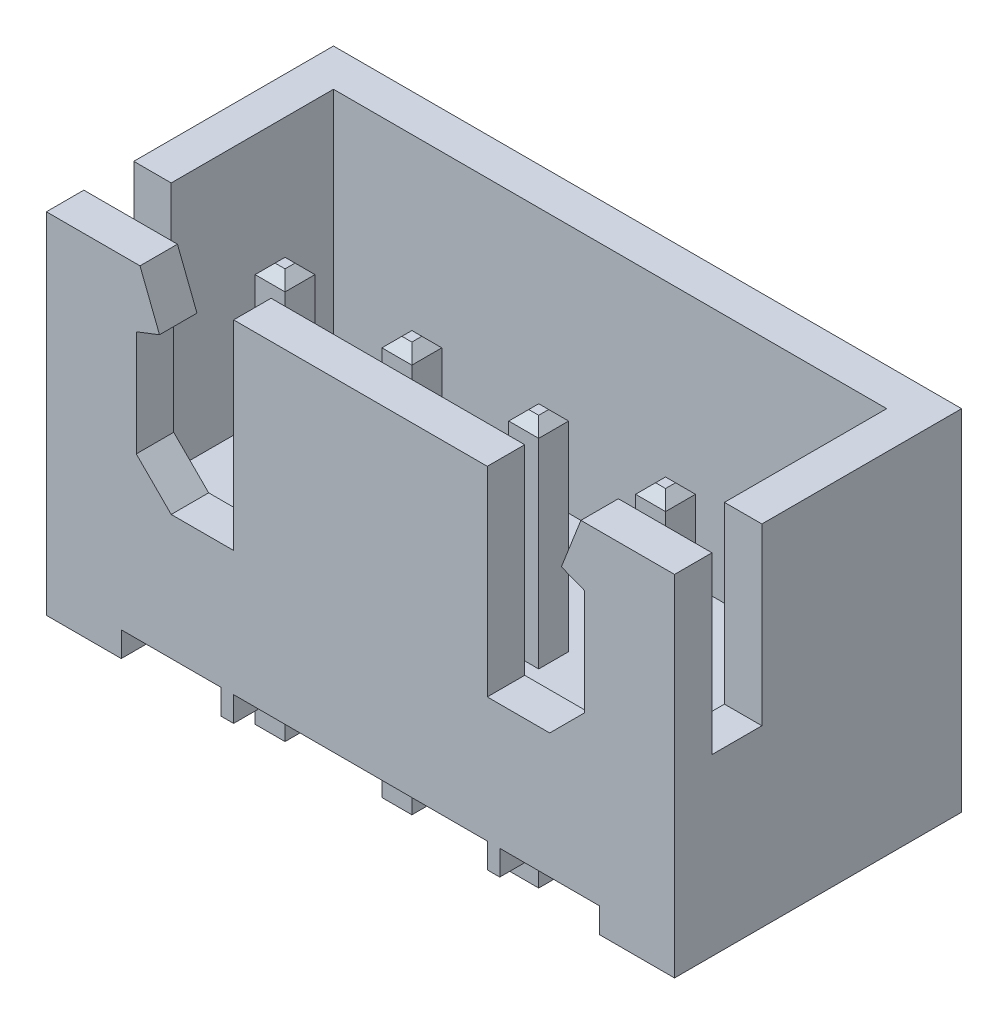
SolidWorks part; units mm, degrees
note: The reader was unsure of these and kept them because the rebuilt part matched: shared geometry of "Sketch8<2>".
ref_plane "Front Plane" through (0, 0, 0) normal (0, 0, 1) x (1, 0, 0)
ref_plane "Top Plane" through (0, 0, 0) normal (0, 1, 0) x (1, 0, 0)
ref_plane "Right Plane" through (0, 0, 0) normal (1, 0, 0) x (0, 0, -1)
sketch "Sketch1" plane through (0, 0, 0) normal (0, 1, 0) x (1, 0, 0)
  line L1 (0, 5.75) -> (3.75, 5.75)
  line L2 (0, 5.75) -> (0, 0)
  line L3 (0, 0) -> (3.75, 0)
  line L4 (3.75, 5.75) -> (3.75, 0)
  line L5 (0, 5.75) -> (3.75, 0) construction
  line L6 (0, 0) -> (3.75, 5.75) construction
  dimension "D1" = 5.75
  dimension "D2" = 3.75
extrude "Boss-Extrude1" add sketch "Sketch1" along normal blind 7
sketch "Sketch2" plane through (0, 7, 0) normal (0, 1, 0) x (1, 0, 0)
  line L4 (3, 5) -> (3.75, 5)
  line L5 (3.75, 0) -> (3.75, 5.75) construction
  line L6 (3.75, 5) -> (3.75, 0.75)
  line L7 (3.75, 0.75) -> (3, 0.75)
  line L8 (3, 0.75) -> (3, 5)
  line L9 (3, 5) -> (0.75, 5)
  line L10 (0.75, 5) -> (0.75, 0.75)
  line L11 (0.75, 0.75) -> (3, 0.75)
  line L13 (3, 5) -> (0.75, 5)
  line L14 (0.75, 5) -> (0.75, 0.75)
  line L15 (0.75, 0.75) -> (3, 0.75)
  dimension "D1" = 0.75
extrude "Cut-Extrude1" cut sketch "Sketch2" against normal blind 5
sketch "Sketch4" plane through (0, 0, 0) normal (0, 0, 1) x (1, 0, 0)
  line L0 (0, 0) -> (3.75, 0) construction
  line L1 (1.5, 0) -> (3.5, 0)
  line L2 (1.5, 0) -> (1.5, 0.5)
  line L3 (1.5, 0.5) -> (3.5, 0.5)
  line L4 (3.5, 0) -> (3.5, 0.5)
  line L5 (3.75, 7) -> (3.75, 0) construction
  line L6 (0, 7) -> (0, 0) construction
  dimension "D1" = 0.5
  dimension "D2" = 0.25
  dimension "D3" = 1.5
extrude "Cut-Extrude2" cut sketch "Sketch4" against normal through all
sketch "Sketch5" plane through (0, 0, 0) normal (0, 0, 1) x (1, 0, 0)
  line L0 (1.8, 3.7) -> (2.5, 3)
  line L1 (2.5, 3) -> (3.75, 3)
  line L2 (3.75, 7) -> (3.75, 0) construction
  line L3 (1.8, 3.7) -> (1.8, 5.818)
  line L4 (1.8, 5.818) -> (2.2657, 6)
  line L5 (2.2657, 6) -> (1.875, 7)
  line L6 (0, 7) -> (3.75, 7) construction
  line L7 (1.875, 7) -> (3.75, 7)
  line L8 (3.75, 7) -> (3.75, 3)
  line L9 (0, 7) -> (0, 0) construction
  line L10 (0, 0) -> (1.5, 0) construction
  dimension "D1" = 1.8
  dimension "D2" = 1
  dimension "D3" = 3
  dimension "D4" = 135
  dimension "D5" = 2.5
  dimension "D6" = 0.5
extrude "Cut-Extrude3" cut sketch "Sketch5" against normal up to next
sketch "Sketch6" plane through (0, 2, 0) normal (0, 1, 0) x (1, 0, 0)
  line L0 (3.75, 0.75) -> (3.75, 5) construction
  line L1 (2.18, 2.6) -> (2.78, 2.6)
  line L2 (2.18, 2.6) -> (2.18, 2)
  line L3 (2.18, 2) -> (2.78, 2)
  line L4 (2.78, 2.6) -> (2.78, 2)
  point P4 (2.48, 2.6)
  dimension "D1" = 0.6
  dimension "D2" = 0.6
  dimension "D3" = 2
  dimension "D4" = 1.27
extrude "Boss-Extrude2" add sketch "Sketch6" along normal offset from surface 0.8 and the other way offset from surface (4 mm away) 2 separate body up to face at (1.5938, 7, -2.875) other way up to face at (0.75, 0, -2.875)
chamfer "Chamfer1" distance 0.2 angle 45 8 edges at (2.48, 6.2, -2.6) (2.18, 6.2, -2.3) (2.48, 6.2, -2) (2.78, 6.2, -2.3) (2.48, -2, -2) (2.78, -2, -2.3) (2.48, -2, -2.6) (2.18, -2, -2.3)
mirror "Mirror2" [suppressed]
mirror "Mirror1" [suppressed]
sketch "Sketch7" plane through (0, 0, 0) normal (1, 0, 0) x (0, 0, -1)
  line L6 (5.75, 7) -> (0, 7) construction
  line L7 (1.75, 7) -> (0.75, 7)
  line L8 (1.75, 7) -> (1.75, 3.5)
  line L9 (1.75, 3.5) -> (0.75, 3.5)
  line L10 (0.75, 7) -> (0.75, 3.5)
  line L11 (0, 7) -> (0, 0) construction
  dimension "D1" = 1
  dimension "D2" = 0.75
  dimension "D3" = 3.5
pattern_linear "LPattern1" [suppressed] count 3 spacing 2.54
ref_plane "Plane1" [suppressed] through (5.02, 0, 0) normal (1, 0, 0) x (0, 0, -1)
mirror "Mirror3" [suppressed] about plane through (5.02, 0, 0) normal (1, 0, 0)
sketch "Sketch8" plane through (3.75, 0, 0) normal (1, 0, 0) x (0, 0, -1)
  line L0 (0, 0.5) -> (5.75, 0.5)
  line L1 (0.75, 7) -> (0, 7) construction
  line L3 (0, 3) -> (0, 7)
  line L4 (0, 7) -> (0.75, 7)
  line L5 (0.75, 3) -> (0.75, 7)
  line L8 (0.75, 2) -> (0.75, 3)
  line L9 (0.75, 3) -> (0, 3)
  line L10 (0, 3) -> (0, 0)
  line L11 (0, 0) -> (5.75, 0)
  line L12 (5.75, 0) -> (5.75, 7)
  line L13 (5.75, 7) -> (5, 7)
  line L14 (5, 7) -> (5, 2)
  line L15 (5, 2) -> (0.75, 2)
  line L16 (0.75, 2) -> (0.75, 3)
  line L18 (0, 3) -> (0, 0.5)
  line L20 (5.75, 0.5) -> (5.75, 7)
  line L21 (5.75, 7) -> (5, 7)
  line L22 (5, 7) -> (5, 2)
  line L23 (5, 2) -> (0.75, 2)
  dimension "D1" = 0
extrude "Boss-Extrude3" [suppressed] add sketch "Sketch8" along normal up to surface (2.54 mm away)
pattern_linear "LPattern3" count 4 spacing 2.54 along (1, 0, 0) of "Boss-Extrude2"
chamfer "Chamfer2" distance 0.2 angle 45 8 edges at (5.02, -2, -2) (5.32, -2, -2.3) (5.02, -2, -2.6) (4.72, -2, -2.3) (5.32, 6.2, -2.3) (5.02, 6.2, -2) (4.72, 6.2, -2.3) (5.02, 6.2, -2.6)
chamfer "Chamfer3" distance 0.2 angle 45 8 edges at (7.86, 6.2, -2.3) (7.56, 6.2, -2) (7.26, 6.2, -2.3) (7.56, 6.2, -2.6) (7.56, -2, -2) (7.86, -2, -2.3) (7.56, -2, -2.6) (7.26, -2, -2.3)
chamfer "Chamfer4" distance 0.2 angle 45 8 edges at (10.1, -2, -2) (10.4, -2, -2.3) (10.1, -2, -2.6) (9.8, -2, -2.3) (10.4, 6.2, -2.3) (10.1, 6.2, -2) (9.8, 6.2, -2.3) (10.1, 6.2, -2.6)
ref_plane "Plane2" through (6.29, 0, 0) normal (1, 0, 0) x (0, 0, -1)
mirror "Mirror4" about plane through (6.29, 0, 0) normal (1, 0, 0) of bodies 104
extrude "Boss-Extrude4" add sketch "Sketch8<2>" along normal up to surface (5.08 mm away)
sketch "Sketch8<2>" plane through (3.75, 0, 0) normal (1, 0, 0) x (0, 0, -1) same geometry as "Sketch8"
extrude "Cut-Extrude4" cut sketch "Sketch7" along normal through all
ref_plane "Plane3" [suppressed] through (3.75, 0, 0) normal (1, 0, 0) x (0, 0, -1)
